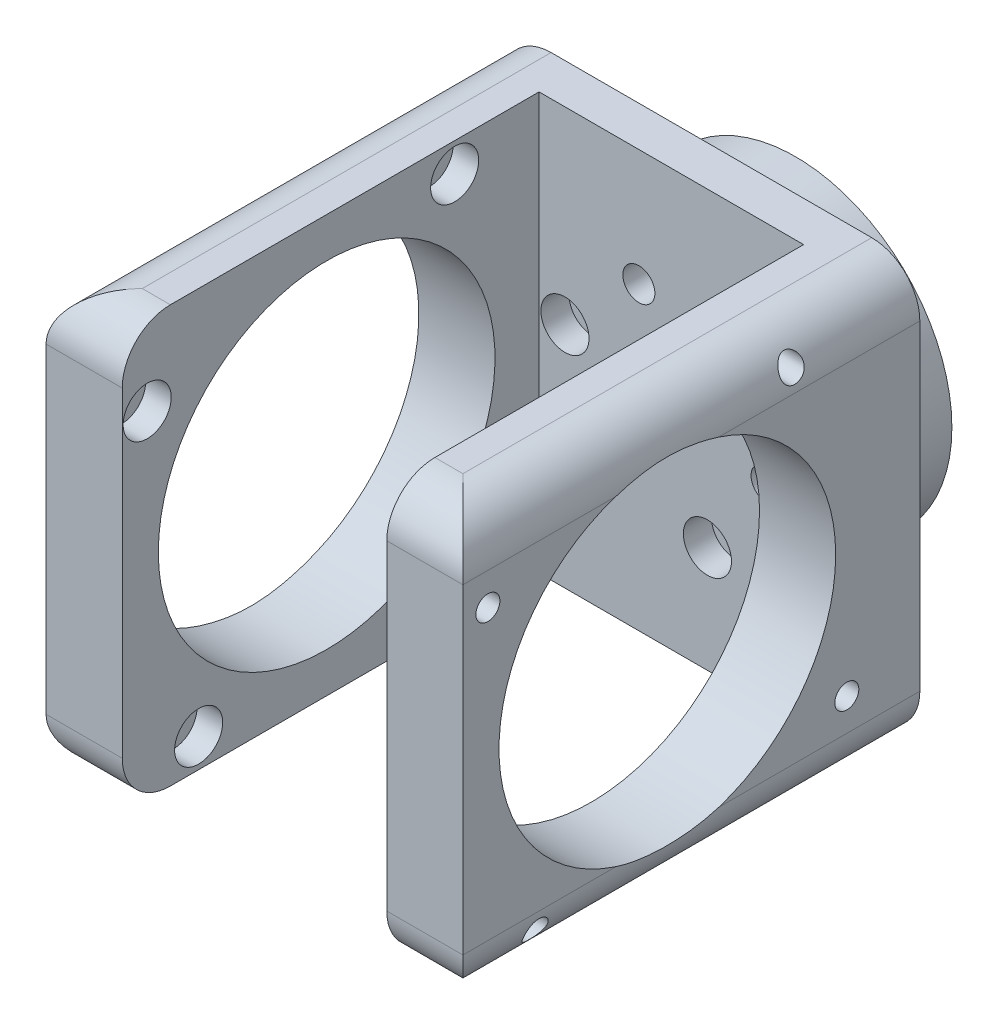
SolidWorks part; units mm, degrees
material "6061 合金"
ref_plane "前视基准面" through (0, 0, 0) normal (0, 0, 1) x (1, 0, 0)
ref_plane "上视基准面" through (0, 0, 0) normal (0, 1, 0) x (1, 0, 0)
ref_plane "右视基准面" through (0, 0, 0) normal (1, 0, 0) x (0, 0, -1)
sketch "草图1" plane through (0, 0, 0) normal (0, 0, 1) x (1, 0, 0)
  arc A3 (-6.5006, 18.3846) -> (6.5006, -18.3846) centre (0, 0) ccw
  arc A4 (6.5006, -18.3846) -> (-6.5006, 18.3846) centre (0, 0) ccw
  arc A5 (-6.5006, 18.3846) -> (6.5006, -18.3846) centre (0, 0) ccw
  arc A6 (6.5006, -18.3846) -> (-6.5006, 18.3846) centre (0, 0) ccw
  circle A7 centre (-4.0503, 11.455) radius 2
  circle A8 centre (8.7724, 10.2613) radius 1.25
  circle A9 centre (11.9455, -2.2198) radius 2
  circle A10 centre (4.5004, -12.7278) radius 1.25
  circle A11 centre (-7.8952, -9.2352) radius 2
  circle A12 centre (-13.2728, 2.4664) radius 1.25
  dimension "D1" = 0
extrude "凸台-拉伸1" add sketch "草图1" along normal blind 10.5
sketch "草图2" plane through (0, 0, 10.5) normal (0, 0, 1) x (1, 0, 0)
  line L1 (20, -26) -> (-20, -26)
  line L2 (26, -20) -> (26, 20)
  line L3 (20, 26) -> (-20, 26)
  line L4 (-26, -20) -> (-26, 20)
  line L5 (26, -26) -> (-26, 26) construction
  line L6 (26, 26) -> (-26, -26) construction
  line L7 (7.5, -26) -> (-7.5, -26) construction
  line L8 (7.5, -26) -> (7.5, 26) construction
  line L9 (7.5, 26) -> (-7.5, 26) construction
  line L10 (-7.5, -26) -> (-7.5, 26) construction
  line L11 (7.5, -26) -> (-7.5, 26) construction
  line L12 (7.5, 26) -> (-7.5, -26) construction
  arc A0 (26, 20) -> (20, 26) centre (20, 20) ccw
  arc A1 (-20, 26) -> (-26, 20) centre (-20, 20) ccw
  arc A2 (-20, -26) -> (-26, -20) centre (-20, -20) cw
  arc A3 (20, -26) -> (26, -20) centre (20, -20) ccw
  circle A4 centre (4.5004, -12.7278) radius 1.25
  circle A5 centre (-7.8952, -9.2352) radius 2
  circle A6 centre (-13.2728, 2.4664) radius 1.25
  circle A7 centre (-4.0503, 11.455) radius 2
  circle A8 centre (11.9455, -2.2198) radius 2
  circle A9 centre (8.7724, 10.2613) radius 1.25
  point P0 (0, 0)
  point P6 (0, 0)
  dimension "D3" = 6
  dimension "D1" = 15
  dimension "D2" = 52
extrude "凸台-拉伸2" add sketch "草图2" along normal blind 5
sketch "草图3" plane through (0, 0, 15.5) normal (0, 0, 1) x (1, 0, 0)
  circle A0 centre (4.5004, -12.7278) radius 3
  circle A1 centre (-13.2728, 2.4664) radius 3
  circle A2 centre (8.7724, 10.2613) radius 3
  dimension "D1" = 6
extrude "切除-拉伸1" cut sketch "草图3" against normal blind 3.5
chamfer "倒角1" distance 2 angle 45 1 edges at (19.5, 0, 10.5)
sketch "草图4" plane through (0, 0, 15.5) normal (0, 0, 1) x (1, 0, 0)
  line L0 (-26, 20) -> (-26, -20) construction
  line L1 (-16.5, -26) -> (-20, -26)
  line L2 (-16.5, -26) -> (-16.5, 26)
  line L3 (-16.5, 26) -> (-20, 26)
  line L4 (-26, -20) -> (-26, 20)
  line L5 (-16.5, -26) -> (-26, 26) construction
  line L6 (-16.5, 26) -> (-26, -26) construction
  line L7 (-20, -26) -> (20, -26) construction
  line L8 (20, 26) -> (-20, 26) construction
  line L9 (0, 0) -> (0, 65.1184) construction
  line L10 (16.5, 26) -> (20, 26)
  line L11 (26, -20) -> (26, 20)
  line L12 (16.5, -26) -> (20, -26)
  line L13 (16.5, -26) -> (16.5, 26)
  arc A1 (-20, 26) -> (-26, 20) centre (-20, 20) ccw
  arc A2 (-20, -26) -> (-26, -20) centre (-20, -20) cw
  arc A3 (20, 26) -> (26, 20) centre (20, 20) cw
  arc A4 (20, -26) -> (26, -20) centre (20, -20) ccw
  point P0 (-21.25, 0)
  dimension "D1" = 6
  dimension "D2" = 9.5
extrude "凸台-拉伸3" add sketch "草图4" along normal blind 52
sketch "草图5" plane through (-26, 0, 0) normal (-1, 0, 0) x (0, 0, 1)
  line L0 (67.5, -26) -> (10.5, -26) construction
  line L1 (67.5, 20) -> (67.5, -20) construction
  line L2 (0, 0) -> (79.4833, 0) construction
  line L3 (61.5, -26) -> (67.5, -26)
  line L4 (67.5, -26) -> (67.5, -20)
  line L5 (61.5, 26) -> (67.5, 26)
  line L6 (67.5, 26) -> (67.5, 20)
  arc A0 (61.5, -26) -> (67.5, -20) centre (61.5, -20) ccw
  arc A1 (61.5, 26) -> (67.5, 20) centre (61.5, 20) cw
  dimension "D1" = 6
extrude "切除-拉伸2" cut sketch "草图5" against normal through all both and the other way through all
sketch "草图6" plane through (0, -26, 0) normal (0, -1, 0) x (1, 0, 0)
  line L0 (26, 67.5) -> (26, 10.5) construction
  line L1 (26, 67.5) -> (16.5, 67.5) construction
  line L2 (0, 0) -> (0, 46.1394) construction
  line L3 (26, 61.5) -> (26, 67.5)
  line L4 (26, 67.5) -> (20, 67.5)
  line L5 (-26, 61.5) -> (-26, 67.5)
  line L6 (-26, 67.5) -> (-20, 67.5)
  arc A0 (26, 61.5) -> (20, 67.5) centre (20, 61.5) ccw
  arc A1 (-26, 61.5) -> (-20, 67.5) centre (-20, 61.5) cw
  dimension "D1" = 6
extrude "切除-拉伸3" [suppressed] cut sketch "草图6" against normal through all both and the other way through all
sketch "草图7" plane through (-16.5, 0, 0) normal (1, 0, 0) x (0, 0, -1)
  circle A0 centre (-42, 0) radius 21
  dimension "D1" = 42
  dimension "D2" = 42
extrude "切除-拉伸4" cut sketch "草图7" against normal through all both and the other way through all
sketch "草图8" plane through (-16.5, 0, 0) normal (1, 0, 0) x (0, 0, -1)
  circle A0 centre (-57.9693, -22.3882) radius 1.5
  circle A1 centre (-19.6118, -15.9693) radius 1.5
  circle A2 centre (-26.0307, 22.3882) radius 1.5
  circle A3 centre (-64.3882, 15.9693) radius 1.5
  dimension "D1" = 3
extrude "切除-拉伸5" cut sketch "草图8" against normal through all both and the other way through all
sketch "草图10" plane through (-16.5, 0, 0) normal (1, 0, 0) x (0, 0, -1)
  circle A0 centre (-64.3882, 15.9693) radius 3
  circle A1 centre (-26.0307, 22.3882) radius 3
  circle A2 centre (-19.6118, -15.9693) radius 3
  circle A3 centre (-57.9693, -22.3882) radius 3
  dimension "D1" = 6
extrude "切除-拉伸6" cut sketch "草图10" against normal blind 3.2
extrude "切除-拉伸8" cut sketch "草图10<2>" along normal blind 3.2 from surface starting at face at (16.5, -22.3882, 56.4693)
sketch "草图10<2>" plane through (-16.5, 0, 0) normal (1, 0, 0) x (0, 0, -1) same geometry as "草图10"
